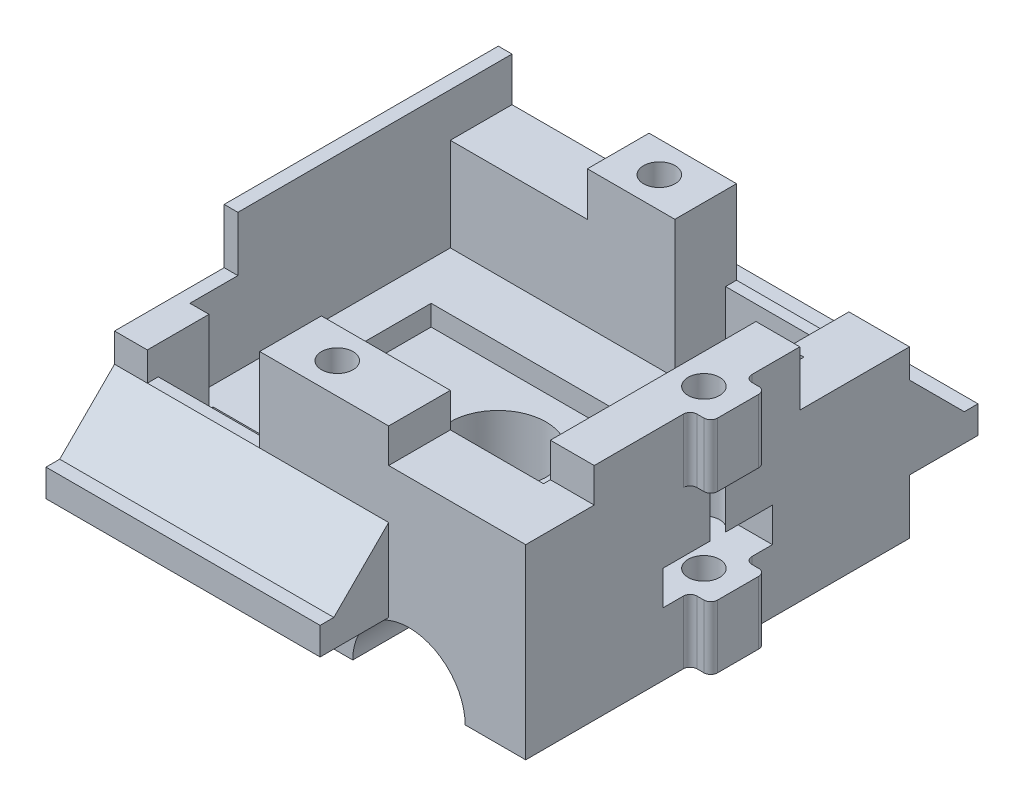
SolidWorks part; units mm, degrees
ref_plane "Front Plane" through (0, 0, 0) normal (0, 0, 1) x (1, 0, 0)
ref_plane "Top Plane" through (0, 0, 0) normal (0, 1, 0) x (1, 0, 0)
ref_plane "Right Plane" through (0, 0, 0) normal (1, 0, 0) x (0, 0, -1)
sketch "Sketch1" plane through (0, 0, 0) normal (1, 0, 0) x (0, 0, -1)
  line L0 (-26.7015, -9.0408) -> (-32.3015, -9.0408) construction
  line L1 (-60.7015, 7.0592) -> (-32.7015, 7.0592)
  line L2 (-60.7015, 7.0592) -> (-60.7015, -9.0408)
  line L3 (-60.7015, -9.0408) -> (-32.7015, -9.0408)
  line L4 (-32.7015, 7.0592) -> (-32.7015, -9.0408)
  dimension "D1" = 16.1
  dimension "D2" = 28
extrude "Boss-Extrude1" add sketch "Sketch1" along normal blind 30
sketch "Sketch2" plane through (0, 0, 60.7015) normal (0, 0, 1) x (1, 0, 0)
  line L7 (30, 7.0592) -> (20, 7.0592)
  line L8 (30, 7.0592) -> (30, 4.5592)
  line L9 (30, 4.5592) -> (20, 4.5592)
  line L10 (20, 7.0592) -> (20, 4.5592)
  dimension "D1" = 10
  dimension "D2" = 2.5
extrude "Cut-Extrude1" cut sketch "Sketch2" against normal blind 5
sketch "Sketch3" plane through (0, 0, 60.7015) normal (0, 0, 1) x (1, 0, 0)
  line L0 (0, 7.0592) -> (0, -9.0408) construction
  line L1 (0, 3.0592) -> (10, 3.0592)
  line L2 (0, 3.0592) -> (0, 7.0592)
  line L3 (0, 7.0592) -> (10, 7.0592)
  line L4 (10, 3.0592) -> (10, 7.0592)
  line L5 (20, 7.0592) -> (0, 7.0592) construction
  dimension "D1" = 4
  dimension "D2" = 10
extrude "Cut-Extrude2" cut sketch "Sketch3" against normal blind 8
sketch "Sketch4" plane through (0, 0, 32.7015) normal (0, 0, -1) x (-1, 0, 0)
  line L6 (-30, 7.0592) -> (0, 7.0592) construction
  line L7 (-1, 7.0592) -> (-11, 7.0592)
  line L8 (-1, 7.0592) -> (-1, 3.8592)
  line L9 (-1, 3.8592) -> (-11, 3.8592)
  line L10 (-11, 7.0592) -> (-11, 3.8592)
  line L11 (0, -9.0408) -> (0, 7.0592) construction
  dimension "D1" = 10
  dimension "D2" = 1
  dimension "D3" = 3.2
extrude "Cut-Extrude3" cut sketch "Sketch4" against normal blind 8
sketch "Sketch5" plane through (0, 0, 32.7015) normal (0, 0, -1) x (-1, 0, 0)
  line L0 (-30, -9.0408) -> (-30, 7.0592) construction
  line L1 (-30, 3.0592) -> (-19, 3.0592)
  line L2 (-30, 3.0592) -> (-30, 7.0592)
  line L3 (-30, 7.0592) -> (-19, 7.0592)
  line L4 (-19, 3.0592) -> (-19, 7.0592)
  line L5 (-30, 7.0592) -> (-11, 7.0592) construction
  dimension "D1" = 4
  dimension "D2" = 11
extrude "Cut-Extrude4" cut sketch "Sketch5" against normal blind 8
sketch "Sketch6" plane through (0, 0, 32.7015) normal (0, 0, -1) x (-1, 0, 0)
  line L0 (-6.4923, -5.0408) -> (-24.9923, -5.0408) construction
  line L1 (-30, -3.0408) -> (-10, -3.0408)
  line L2 (-30, -3.0408) -> (-30, -5.0408)
  line L3 (-30, -5.0408) -> (-10, -5.0408)
  line L4 (-10, -3.0408) -> (-10, -5.0408)
  line L5 (-30, -9.0408) -> (-30, 3.0592) construction
  line L6 (0, -9.0408) -> (0, 7.0592) construction
  dimension "D1" = 0
  dimension "D2" = 10
  dimension "D3" = 2
extrude "Boss-Extrude2" add sketch "Sketch6" along normal blind 5
chamfer "Chamfer1" distance 4 angle 45 1 edges at (20, -3.0408, 32.7015)
sketch "Sketch7" plane through (0, 0, 60.7015) normal (0, 0, 1) x (1, 0, 0)
  line L0 (21.4823, -5.0408) -> (2.9823, -5.0408) construction
  line L1 (0, -3.0408) -> (20, -3.0408)
  line L2 (0, -3.0408) -> (0, -5.0408)
  line L3 (0, -5.0408) -> (20, -5.0408)
  line L4 (20, -3.0408) -> (20, -5.0408)
  line L5 (30, 4.5592) -> (30, -9.0408) construction
  line L6 (0, 3.0592) -> (0, -9.0408) construction
  dimension "D1" = 10
  dimension "D2" = 0
  dimension "D3" = 2
extrude "Boss-Extrude3" add sketch "Sketch7" along normal blind 5
chamfer "Chamfer2" distance 4 angle 45 1 edges at (10, -3.0408, 60.7015)
sketch "Sketch9" plane through (0, 7.0592, 0) normal (0, 1, 0) x (1, 0, 0)
  line L0 (1, -40.7015) -> (1, -32.7015) construction
  line L1 (1, -37.2015) -> (26.8, -37.2015)
  line L2 (1, -37.2015) -> (1, -56.2015)
  line L3 (1, -56.2015) -> (26.8, -56.2015)
  line L4 (26.8, -37.2015) -> (26.8, -56.2015)
  line L5 (30, -32.7015) -> (19, -32.7015) construction
  line L6 (20, -60.7015) -> (10, -60.7015) construction
  line L7 (30, -40.7015) -> (30, -55.7015) construction
  dimension "D1" = 4.5
  dimension "D2" = 4.5
  dimension "D3" = 3.2
extrude "Cut-Extrude6" cut sketch "Sketch9" against normal blind 10
sketch "Sketch13" plane through (0, 0, 60.7015) normal (0, 0, 1) x (1, 0, 0)
  circle A0 centre (21.4823, -9.0408) radius 4.1
  dimension "D1" = 8.2
extrude "Cut-Extrude10" cut sketch "Sketch13" against normal blind 27.2
sketch "Sketch14" plane through (0, 0, 32.7015) normal (0, 0, -1) x (-1, 0, 0)
  circle A0 centre (-6.4923, -9.0408) radius 4.1
  dimension "D1" = 8.2
extrude "Cut-Extrude11" cut sketch "Sketch14" against normal blind 27.2
sketch "Sketch15" plane through (0, -9.0408, 0) normal (0, -1, 0) x (1, 0, 0)
  line L0 (10.5923, 59.9015) -> (10.5923, 32.7015) construction
  line L1 (2.3923, 59.9015) -> (10.5923, 59.9015)
  line L2 (2.3923, 59.9015) -> (2.3923, 55.9015)
  line L3 (2.3923, 55.9015) -> (10.5923, 55.9015)
  line L4 (10.5923, 59.9015) -> (10.5923, 55.9015)
  line L5 (25.5823, 60.7015) -> (25.5823, 33.5015) construction
  line L6 (17.3823, 33.5015) -> (25.5823, 33.5015)
  line L7 (17.3823, 33.5015) -> (17.3823, 37.5015)
  line L8 (17.3823, 37.5015) -> (25.5823, 37.5015)
  line L9 (25.5823, 33.5015) -> (25.5823, 37.5015)
  dimension "D1" = 4
  dimension "D2" = 4
extrude "Cut-Extrude12" cut sketch "Sketch15" against normal blind 27.2
sketch "Sketch16" plane through (0, 7.0592, 0) normal (0, 1, 0) x (1, 0, 0)
  line L1 (10.5923, -59.9015) -> (10, -59.9015)
  line L2 (10.5923, -59.9015) -> (10.5923, -60.7015)
  line L3 (10.5923, -60.7015) -> (10, -60.7015)
  line L4 (10, -59.9015) -> (10, -60.7015)
  line L5 (17.3823, -33.5015) -> (19, -33.5015)
  line L6 (17.3823, -33.5015) -> (17.3823, -32.7015)
  line L7 (17.3823, -32.7015) -> (19, -32.7015)
  line L8 (19, -33.5015) -> (19, -32.7015)
extrude "Cut-Extrude13" cut sketch "Sketch16" against normal up to surface (4 mm away) up to face at (25.3456, 3.0592, 36.0265)
sketch "Sketch17" plane through (0, -9.0408, 0) normal (0, -1, 0) x (1, 0, 0)
  line L0 (30, 60.7015) -> (30, 32.7015) construction
  line L1 (30, 48.7015) -> (31.5, 48.7015)
  line L2 (30, 48.7015) -> (30, 44.7015)
  line L3 (30, 44.7015) -> (31.5, 44.7015)
  line L4 (31.5, 48.7015) -> (31.5, 44.7015)
  line L5 (30, 32.7015) -> (10.5923, 32.7015) construction
  line L6 (30, 60.7015) -> (25.5823, 60.7015) construction
  dimension "D1" = 12
  dimension "D2" = 12
  dimension "D3" = 1.5
extrude "Boss-Extrude4" add sketch "Sketch17" against normal up to surface (16.1 mm away) up to face at (28.4, 7.0592, 48.2015)
fillet "Fillet1" radius 0.5 4 edges at (30, -0.9908, 44.7015) (31.5, -0.9908, 44.7015) (31.5, -0.9908, 48.7015) (30, -0.9908, 48.7015)
sketch "Sketch18" plane through (0, -9.0408, 0) normal (0, -1, 0) x (1, 0, 0)
  line L0 (17.3823, 60.7015) -> (0, 60.7015) construction
  line L1 (0, 60.7015) -> (0, 32.7015) construction
  circle A0 centre (13.985, 46.7015) radius 3.5
  dimension "D1" = 14
  dimension "D2" = 13.985
  dimension "D3" = 7
extrude "Cut-Extrude14" cut sketch "Sketch18" against normal up to surface (6.1 mm away) up to face at (13.9582, -2.9408, 46.7015)
sketch "Sketch19" plane through (31.5, 0, 0) normal (1, 0, 0) x (0, 0, -1)
  line L0 (-32.7015, 0.9592) -> (-32.7015, 3.0592) construction
  line L1 (-50.7015, -1.9408) -> (-42.7015, -1.9408)
  line L2 (-50.7015, -1.9408) -> (-50.7015, -2.9408)
  line L3 (-50.7015, -2.9408) -> (-42.7015, -2.9408)
  line L4 (-42.7015, -1.9408) -> (-42.7015, -2.9408)
  line L5 (-40.7015, 7.0592) -> (-44.2015, 7.0592) construction
  dimension "D1" = 8
  dimension "D2" = 10
  dimension "D3" = 1
  dimension "D4" = 10
extrude "Cut-Extrude15" cut sketch "Sketch19" against normal blind 10
sketch "Sketch20" plane through (0, -2.9408, 0) normal (0, 1, 0) x (1, 0, 0)
  line L0 (10.5923, -56.2015) -> (20, -56.2015) construction
  line L1 (24.3, -41.4015) -> (3.8, -41.4015)
  line L2 (24.3, -41.4015) -> (24.3, -52.0015)
  line L3 (24.3, -52.0015) -> (3.8, -52.0015)
  line L4 (3.8, -41.4015) -> (3.8, -52.0015)
  line L5 (26.8, -55.7015) -> (26.8, -40.7015) construction
  line L6 (17.3823, -37.2015) -> (11, -37.2015) construction
  line L7 (1, -52.7015) -> (1, -32.7015) construction
  dimension "D1" = 4.2
  dimension "D2" = 2.5
  dimension "D3" = 4.2
  dimension "D4" = 2.8
extrude "Cut-Extrude16" cut sketch "Sketch20" against normal blind 1.5
sketch "Sketch21" plane through (0, -2.9408, 0) normal (0, 1, 0) x (1, 0, 0)
  line L0 (24.3, -52.0015) -> (24.3, -41.4015) construction
  line L1 (24.3, -50.7015) -> (30, -50.7015)
  line L2 (24.3, -50.7015) -> (24.3, -42.7015)
  line L3 (24.3, -42.7015) -> (30, -42.7015)
  line L4 (30, -50.7015) -> (30, -42.7015)
extrude "Cut-Extrude17" cut sketch "Sketch21" against normal blind 1.5
sketch "Sketch22" plane through (31.5, 0, 0) normal (1, 0, 0) x (0, 0, -1)
  line L0 (-42.7015, -4.4408) -> (-42.7015, -1.9408) construction
  line L1 (-50.7015, -4.4408) -> (-42.7015, -4.4408)
  line L2 (-50.7015, -4.4408) -> (-50.7015, 2.4146)
  line L3 (-50.7015, 2.4146) -> (-42.7015, 2.4146)
  line L4 (-42.7015, -4.4408) -> (-42.7015, 2.4146)
extrude "Cut-Extrude18" cut sketch "Sketch22" against normal blind 1.5
sketch "Sketch23" plane through (0, 7.0592, 0) normal (0, 1, 0) x (1, 0, 0)
  circle A0 centre (29, -46.7015) radius 1.15
  circle A1 centre (14, -34.9515) radius 1.15
  circle A2 centre (14, -58.4515) radius 1.15
  dimension "D1" = 2.3
  dimension "D2" = 2.3
  dimension "D3" = 2.3
extrude "Cut-Extrude19" cut sketch "Sketch23" against normal through all
sketch "Sketch24" plane through (0, 3.0592, 0) normal (0, 1, 0) x (1, 0, 0)
  line L1 (25.5823, -33.5015) -> (17.3823, -33.5015)
  line L2 (25.5823, -33.5015) -> (25.5823, -32.7015)
  line L3 (25.5823, -32.7015) -> (17.3823, -32.7015)
  line L4 (17.3823, -33.5015) -> (17.3823, -32.7015)
  line L5 (2.3923, -59.9015) -> (10.5923, -59.9015)
  line L6 (2.3923, -59.9015) -> (2.3923, -60.7015)
  line L7 (2.3923, -60.7015) -> (10.5923, -60.7015)
  line L8 (10.5923, -59.9015) -> (10.5923, -60.7015)
extrude "Cut-Extrude20" cut sketch "Sketch24" against normal blind 2.1
